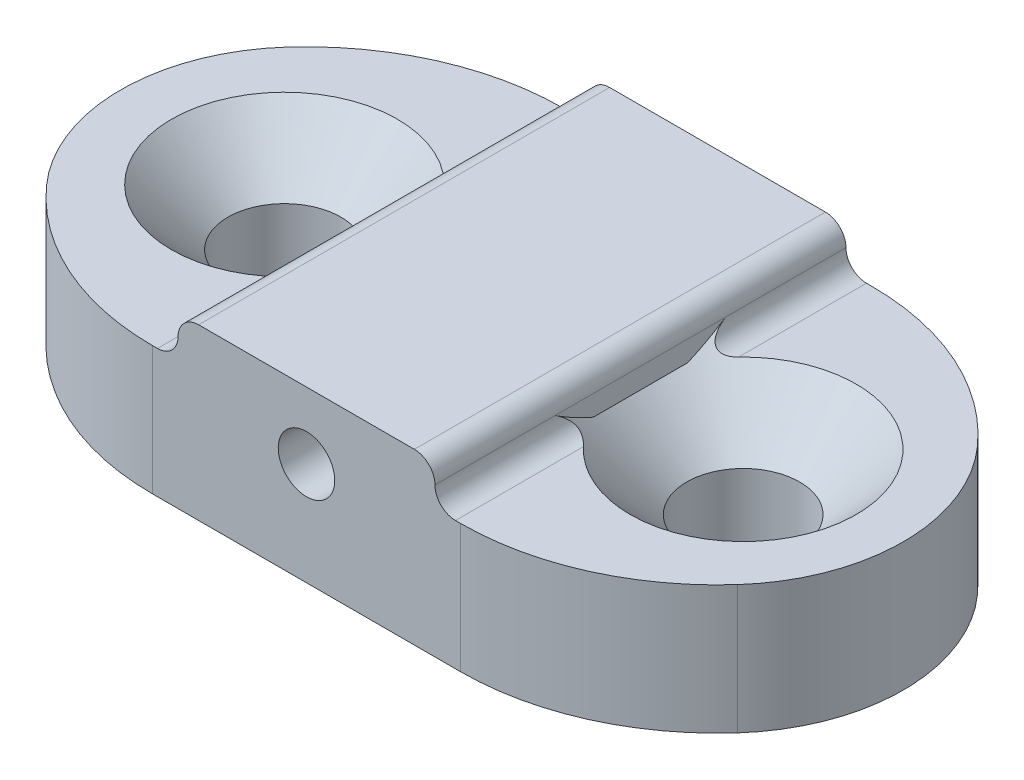
SolidWorks part; units mm, degrees
ref_plane "Front Plane" through (0, 0, 0) normal (0, 0, 1) x (1, 0, 0)
ref_plane "Top Plane" through (0, 0, 0) normal (0, 1, 0) x (1, 0, 0)
ref_plane "Right Plane" through (0, 0, 0) normal (1, 0, 0) x (0, 0, -1)
sketch "Sketch1" plane through (0, 0, 0) normal (0, 1, 0) x (1, 0, 0)
  line L1 (0, 0) -> (16, 0)
  line L2 (0, 0) -> (0, 8)
  line L3 (0, 8) -> (16, 8)
  line L4 (16, 0) -> (16, 8)
  dimension "D1" = 16
  dimension "D2" = 8
extrude "Boss-Extrude1" add sketch "Sketch1" along normal blind 2.5
sketch "Sketch2" plane through (0, 0, 0) normal (0, 0, 1) x (1, 0, 0)
  line L0 (0, 2.5) -> (16, 2.5) construction
  line L1 (5.5, 2.5) -> (10.5, 2.5)
  line L2 (5.5, 2.5) -> (5.5, 3.3)
  line L3 (5.5, 3.3) -> (10.5, 3.3)
  line L4 (10.5, 2.5) -> (10.5, 3.3)
  line L5 (8, 0) -> (8, 3.3) construction
  line L6 (0, 0) -> (16, 0) construction
  point P10 (8, 3.3)
  dimension "D1" = 0.8
  dimension "D2" = 5
extrude "Boss-Extrude2" add sketch "Sketch2" against normal up to surface (8 mm away) up to face at (8, 1.25, -8)
sketch "Sketch3" plane through (0, 0, 0) normal (0, 0, 1) x (1, 0, 0)
  line L0 (8, 3.3) -> (8, 0) construction
  line L1 (10.5, 3.3) -> (5.5, 3.3) construction
  line L2 (0, 0) -> (16, 0) construction
  circle A0 centre (8, 2) radius 0.55
  point P9 (8, 3.3)
  dimension "D1" = 1.1
  dimension "D2" = 2
extrude "Cut-Extrude1" cut sketch "Sketch3" against normal through all both and the other way through all
sketch "Sketch4" plane through (0, 2.5, 0) normal (0, 1, 0) x (1, 0, 0)
  line L0 (12.5, 8) -> (12.5, 4) construction
  line L1 (16, 8) -> (10.5, 8) construction
  line L2 (3.5, 8) -> (3.5, 4) construction
  line L3 (5.5, 8) -> (0, 8) construction
  line L4 (3.5, 4) -> (12.5, 4) construction
  line L5 (16, 0) -> (16, 8) construction
  line L6 (0, 8) -> (0, 0) construction
  point P12 (16, 4)
  dimension "D1" = 3.5
  dimension "D2" = 3.5
hole_wizard "CSK for M2 Countersunk Flat Head Screw1" positions "Sketch5" profile "Sketch6" countersink size "M2" standard "ISO" end condition through all
sketch "Sketch5" plane through (0, 2.5, 0) normal (0, 1, 0) x (1, 0, 0)
  point P0 (3.5711, 4)
  point P2 (12.5, 4)
sketch "Sketch6" plane through (3.5711, 2.5, -4) normal (1, 0, 0) x (0, 0, 1)
  line L0 (0, 0) -> (0, 2.5)
  line L1 (0, 2.5) -> (1.1, 2.5)
  line L2 (1.1, 2.5) -> (1.1, 1.1)
  line L3 (1.1, 1.1) -> (2.2, 0)
  line L5 (2.2, 0) -> (0, 0)
  line L6 (-1.1, 1.1) -> (-2.2, 0) construction
  line L11 (0, -6.35) -> (0, 107.95) construction
  dimension "Thru Hole Dia." = 2.2
  dimension "Thru Hole Depth" = 2.5
  dimension "Near C'Sink Dia." = 4.4
  dimension "Near C'Sink Angle" = 90
fillet "Fillet1" radius 0.4 6 edges at (10.5, 2.5, -6.4583) (10.5, 2.5, -1.5417) (10.5, 3.3, -4) (5.5, 3.3, -4) (5.5, 2.5, -1.471) (5.5, 2.5, -6.529)
fillet "Fillet2" radius 5 4 edges at (16, 1.25, 0) (16, 1.25, -8) (0, 1.25, -8) (0, 1.25, 0)
fillet "Fillet3" radius 3.5 2 edges at (0.101, 1.25, -4) (15.899, 1.25, -4)
